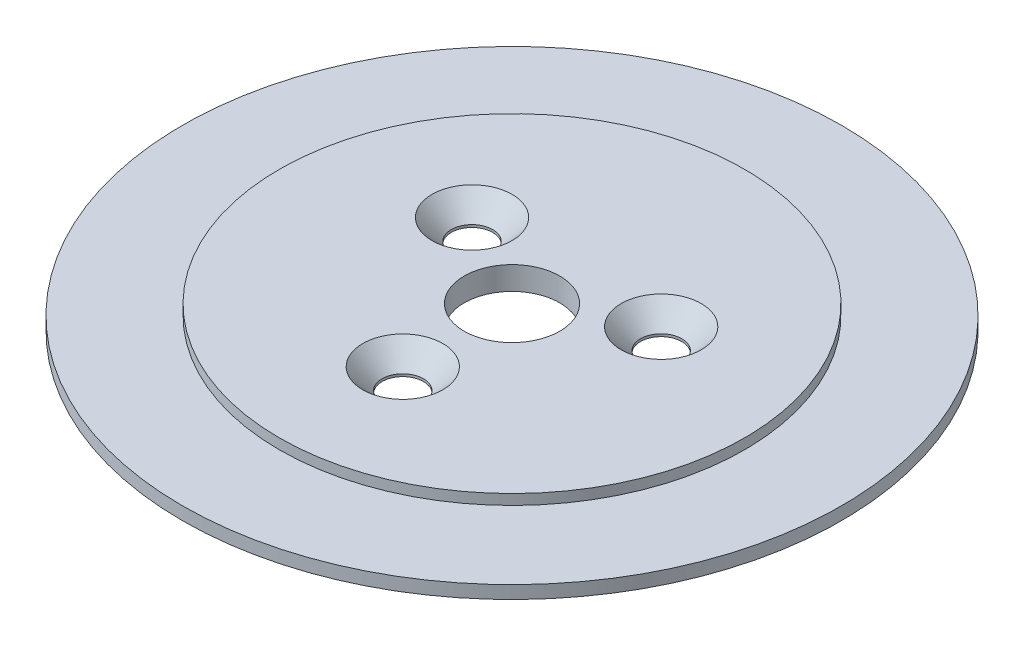
SolidWorks part; units mm, degrees
ref_plane "Front Plane" through (0, 0, 0) normal (0, 0, 1) x (1, 0, 0)
ref_plane "Top Plane" through (0, 0, 0) normal (0, 1, 0) x (1, 0, 0)
ref_plane "Right Plane" through (0, 0, 0) normal (1, 0, 0) x (0, 0, -1)
sketch "Sketch1" plane through (0, 0, 0) normal (0, 1, 0) x (1, 0, 0)
  circle A0 centre (0, 0) radius 25.5
  circle A1 centre (0, 0) radius 3.7
  circle A2 centre (0, 0) radius 18
  dimension "D1" = 51
  dimension "D2" = 7.4
  dimension "D3" = 36
extrude "Boss-Extrude1" add sketch "Sketch1" along normal blind 1 contours A0 A2 | A2 A1 region at (-24.7788, 0, 0) region at (-17.4909, 0, 0)
extrude "Boss-Extrude2" add sketch "Sketch1<3>" along normal blind 1.8 contours A2 A1 region at (-17.4909, 0, 0)
sketch "Sketch1<3>" plane through (0, 0, 0) normal (0, 1, 0) x (1, 0, 0) same geometry as "Sketch1"
sketch "Sketch2" plane through (0, 1.8, 0) normal (0, 1, 0) x (1, 0, 0)
  line L0 (0, 0) -> (0, -8.45) construction
  line L1 (0, 0) -> (-7.3179, 4.225) construction
  line L2 (0, 0) -> (7.3179, 4.225) construction
  point P4 (0, -8.45)
  dimension "D1" = 8.45
  dimension "D2" = 3
hole_wizard "Hole1" positions "3DSketch2" profile "Sketch5" legacy
sketch3d "3DSketch2"
  point P0 (7.3179, 1.8, -4.225)
  point P3 (-7.3179, 1.8, -4.225)
  point P6 (0, 1.8, 8.45)
sketch "Sketch5" plane through (7.3179, 1.8, -4.225) normal (1, 0, 0) x (0, 0, 1)
  line L0 (0, 0) -> (0, 7.8571)
  line L1 (0, 7.8571) -> (1.6, 7.8571)
  line L2 (1.6, 7.8571) -> (1.6, 1.6086)
  line L3 (1.6, 1.6086) -> (3.1, 0)
  line L4 (3.1, 0) -> (0, 0)
  line L5 (0, -6.4453) -> (0, 115.525) construction
  line L6 (-1.6, 1.6086) -> (-3.1, 0) construction
  dimension "Diameter" = 3.2
  dimension "Depth" = 7.999
  dimension "C-Sink Angle" = 86
  dimension "C-Sink Diameter" = 6.2
equation "\"M3 Nut Diameter\" = 5.50mm"
equation "\"Clearance Diameter 3D Printing\" = .20mm"
equation "\"D-Shaft\"= 4mm'D-Shaft diameter"
equation "\"Wheel Axle Diameter\"= 6.8mm'Axle to Connect to Wheel"
equation "\"Wheel Thickness\"= 10mm'Wheel Thickness"
equation "\"M3 Screw Diameter\"= 3.20mm'M3 Screw Diameter already with 3D printing Clearance"
equation "\"Wheel Diameter\"= 60mm"
equation "\"Silicone Tire Width\"= 7mm"
equation "\"D1@Sketch1\"=( \"Wheel Diameter\" - 2 * \"Silicone Tire Width\" ) + 2 * 2.0mm + 1.0mm"
equation "\"D2@Sketch1\"= \"Wheel Axle Diameter\" + .6mm"
equation "\"Logo Diameter\"= 36mm"
equation "\"D3@Sketch1\"= \"Logo Diameter\""
